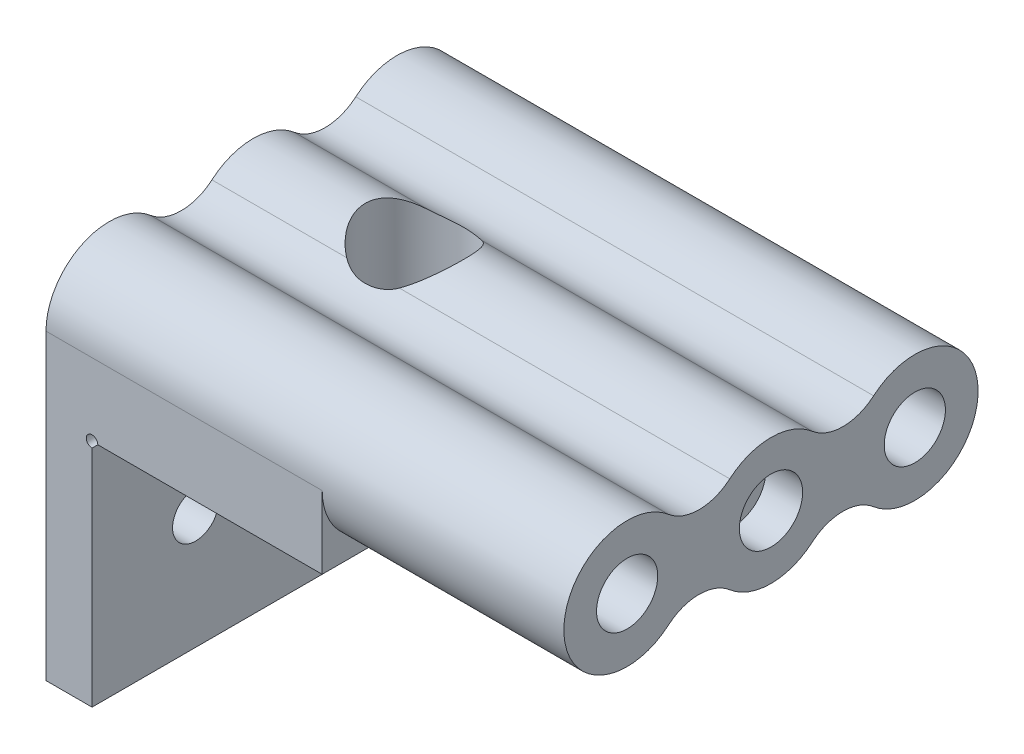
SolidWorks part; units mm, degrees
ref_plane "Front Plane" through (0, 0, 0) normal (0, 0, 1) x (1, 0, 0)
ref_plane "Top Plane" through (0, 0, 0) normal (0, 1, 0) x (1, 0, 0)
ref_plane "Right Plane" through (0, 0, 0) normal (1, 0, 0) x (0, 0, -1)
sketch "Sketch1" plane through (0, 0, 0) normal (0, 0, 1) x (1, 0, 0)
  line L0 (0, 0) -> (4, 0)
  line L1 (55, 0) -> (-55, 0) construction
  line L2 (4, 0) -> (4, 19.5)
  line L3 (4.5, 20) -> (24, 20)
  line L4 (24, 20) -> (24, 24)
  line L5 (24, 24) -> (0, 24)
  line L6 (0, -55) -> (0, 55) construction
  line L7 (0, 24) -> (0, 0)
  line L8 (4, 20) -> (4.5, 20) construction
  line L9 (4, 20) -> (4, 19.5) construction
  arc A0 (4.5, 20) -> (4, 19.5) centre (4, 20) ccw
  point P6 (2, 0)
  dimension "D6" = 0.5
  dimension "D1" = 20
  dimension "D2" = 20
  dimension "D3" = 4
extrude "Boss-Extrude1" add sketch "Sketch1" along normal mid plane 36
sketch "Sketch3" plane through (24, 0, 0) normal (-1, 0, 0) x (0, 0, 1)
  line L0 (12.5, 26.3) -> (-12.5, 26.3) construction
  line L1 (0, -13.2) -> (0, 13.2) construction
  line L2 (18, 20) -> (-18, 20) construction
  arc A0 (8.9193, 22.1253) -> (3.5807, 22.1253) centre (6.25, 19.0132) ccw
  arc A1 (3.5807, 22.1253) -> (-3.5807, 22.1253) centre (0, 26.3) cw
  arc A2 (-3.5807, 22.1253) -> (-8.9193, 22.1253) centre (-6.25, 19.0132) ccw
  arc A3 (-8.9193, 22.1253) -> (-8.9193, 30.4747) centre (-12.5, 26.3) cw
  arc A4 (-8.9193, 30.4747) -> (-3.5807, 30.4747) centre (-6.25, 33.5868) ccw
  arc A5 (-3.5807, 30.4747) -> (3.5807, 30.4747) centre (0, 26.3) cw
  arc A6 (3.5807, 30.4747) -> (8.9193, 30.4747) centre (6.25, 33.5868) ccw
  arc A7 (8.9193, 30.4747) -> (8.9193, 22.1253) centre (12.5, 26.3) cw
  point P19 (0, 26.3)
  dimension "D1" = 5.5
  dimension "D2" = 5.5
  dimension "D5" = 4.1
  dimension "D3" = 25
  dimension "D4" = 6.3
extrude "Boss-Extrude2" add sketch "Sketch3" along normal up to surface (24 mm away) and the other way blind 21 up to face at (0, 12, 0)
sketch "Sketch10" plane through (0, 24, 0) normal (0, 1, 0) x (1, 0, 0)
  line L1 (0, 18) -> (24, 18)
  line L2 (0, 18) -> (0, -18)
  line L3 (0, -18) -> (24, -18)
  line L4 (24, 18) -> (24, -18)
extrude "Boss-Extrude4" add sketch "Sketch10" along normal up to vertex (2.3 mm away) up to point (24, 26.3, 12.5)
sketch "Sketch4" plane through (45, 0, 0) normal (1, 0, 0) x (0, 0, -1)
  circle A0 centre (-12.5, 26.3) radius 2.6605
  circle A1 centre (12.5, 26.3) radius 2.6605
  circle A2 centre (0, 26.3) radius 2.75
  dimension "D1" = 5.321
  dimension "D2" = 5.321
  dimension "D3" = 5.5
extrude "Cut-Extrude1" cut sketch "Sketch4" against normal through all both and the other way through all contours A0 | A1 region at (45, 26.3, 12.5) region at (45, 26.3, -12.5)
extrude "Cut-Extrude2" cut sketch "Sketch4<3>" against normal blind 3.2 contours A2 region at (45, 26.3, 0)
sketch "Sketch4<3>" plane through (45, 0, 0) normal (1, 0, 0) x (0, 0, -1) same geometry as "Sketch4"
sketch "Sketch6" plane through (4, 0, 0) normal (1, 0, 0) x (0, 0, -1)
  line L0 (-18, 0) -> (18, 0) construction
  line L1 (-9, 10) -> (9, 10) construction
  line L2 (0, 17.49) -> (0, -17.49) construction
  line L3 (-18, 0) -> (-18, 19.5) construction
  circle A0 centre (-9, 10) radius 2
  circle A1 centre (9, 10) radius 2
  point P7 (0, 10)
  dimension "D3" = 4
  dimension "D1" = 10
  dimension "D2" = 9
extrude "Cut-Extrude3" cut sketch "Sketch6" against normal through all both and the other way through all
ref_plane "Plane1" through (0, 31.8, 0) normal (0, 1, 0) x (1, 0, 0)
sketch "Sketch8" plane through (0, 31.8, 0) normal (0, 1, 0) x (1, 0, 0)
  line L0 (-17.49, 0) -> (17.49, 0) construction
  line L2 (0, 3.5807) -> (0, -3.5807) construction
  circle A0 centre (14, 0) radius 4.25
  circle A1 centre (14, 0) radius 2
  dimension "D1" = 8.5
  dimension "D2" = 4
  dimension "D3" = 14
extrude "Cut-Extrude4" cut sketch "Sketch8" against normal through all contours A1 region at (14, 31.8, 0)
extrude "Cut-Extrude5" cut sketch "Sketch8<3>" against normal offset from surface (8.8 mm away) 3 contours A0 A1 region at (9.8702, 31.8, 0) up to face at (14, 20, 2)
sketch "Sketch8<3>" plane through (0, 31.8, 0) normal (0, 1, 0) x (1, 0, 0) same geometry as "Sketch8"
